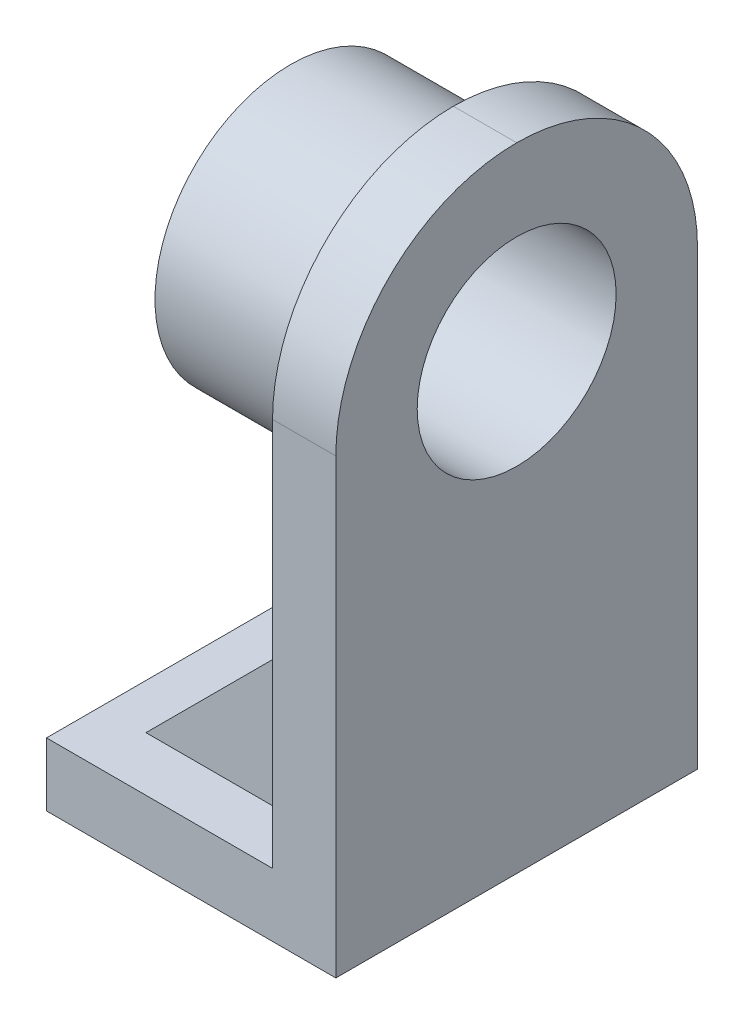
SolidWorks part; units mm, degrees
ref_plane "Front Plane" through (0, 0, 0) normal (0, 0, 1) x (1, 0, 0)
ref_plane "Top Plane" through (0, 0, 0) normal (0, 1, 0) x (1, 0, 0)
ref_plane "Right Plane" through (0, 0, 0) normal (1, 0, 0) x (0, 0, -1)
sketch "Sketch1" plane through (0, 0, 0) normal (0, 0, 1) x (1, 0, 0)
  line L0 (0, 0) -> (-32, 0)
  line L1 (0, 0) -> (0, 70)
  line L2 (-32, 0) -> (-32, 7)
  line L3 (-32, 7) -> (-7, 7)
  line L4 (-7, 7) -> (-7, 70)
  line L5 (-7, 70) -> (0, 70)
  dimension "D1" = 32
  dimension "D2" = 7
  dimension "D3" = 70
  dimension "D4" = 7
extrude "Boss-Extrude1" add sketch "Sketch1" against normal blind 40
fillet "Fillet1" radius 20 2 edges at (-3.5, 70, 0) (-3.5, 70, -40)
sketch "Sketch3" plane through (0, 7, 0) normal (0, 1, 0) x (1, 0, 0)
  line L0 (-7, 6) -> (-27, 6)
  line L1 (-7, 40) -> (-7, 0) construction
  line L6 (-7, 34) -> (-27, 34)
  dimension "D1" = 20
  dimension "D2" = 6
  dimension "D3" = 6
  dimension "D4" = 20
sketch "Sketch4" plane through (-7, 0, 0) normal (-1, 0, 0) x (0, 0, 1)
  line L0 (-6, 7) -> (-6, 27)
  line L1 (-34, 7) -> (-34, 27)
  dimension "D1" = 20
  dimension "D2" = 20
sketch "Sketch5" plane through (0, 7, 0) normal (0, 1, 0) x (1, 0, 0)
  line L0 (-27, 0) -> (-27, 40) construction
  line L1 (-7, 0) -> (-32, 0) construction
  line L2 (-7, 40) -> (-32, 40) construction
sketch "Sketch6" plane through (-7, 0, 0) normal (-1, 0, 0) x (0, 0, 1)
  line L0 (0, 27) -> (-40, 27)
  line L1 (0, 50) -> (0, 7) construction
  line L2 (-40, 50) -> (-40, 7) construction
  line L4 (0, 7) -> (0, 27)
  dimension "D1" = 20
sketch "Sketch7" plane through (0, 0, 0) normal (0, 0, 1) x (1, 0, 0)
  line L0 (-7, 7) -> (-27, 7)
  line L1 (-27, 7) -> (-7, 27)
  line L2 (-7, 27) -> (-7, 7)
extrude "Boss-Extrude2" add sketch "Sketch7" against normal blind 10 contours L1 L2 L0
sketch "Sketch11" plane through (0, 0, 0) normal (0, 0, 1) x (1, 0, 0)
  line L0 (-7, 27) -> (-7, 7)
  line L1 (-7, 7) -> (-27, 7)
  line L2 (-27, 7) -> (-7, 27)
extrude "Cut-Extrude1" cut sketch "Sketch11" against normal blind 6
sketch "Sketch12" plane through (0, 0, -40) normal (0, 0, -1) x (-1, 0, 0)
  line L0 (7, 27) -> (7, 7)
  line L1 (7, 7) -> (27, 7)
  line L2 (27, 7) -> (7, 27)
extrude "Boss-Extrude3" add sketch "Sketch12" against normal blind 10
sketch "Sketch13" plane through (0, 0, -40) normal (0, 0, -1) x (-1, 0, 0)
  line L0 (7, 27) -> (27, 7)
  line L1 (27, 7) -> (7, 7)
  line L2 (7, 7) -> (7, 27)
extrude "Cut-Extrude3" cut sketch "Sketch13" against normal blind 6
sketch "Sketch15" plane through (-7, 0, 0) normal (-1, 0, 0) x (0, 0, 1)
  line L2 (-40, 50) -> (-40, 7) construction
  circle A0 centre (-20, 50) radius 11
  circle A1 centre (-20, 50) radius 15
  point P3 (0, 0)
  dimension "D1" = 22
  dimension "D2" = 30
  dimension "D3" = 50
  dimension "D4" = 20
extrude "Boss-Extrude4" add sketch "Sketch15" along normal blind 18
sketch "Sketch16" plane through (-7, 0, 0) normal (-1, 0, 0) x (0, 0, 1)
  circle A0 centre (-20, 50) radius 11
  point P7 (0, 0)
extrude "Cut-Extrude4" cut sketch "Sketch16" against normal blind 7
